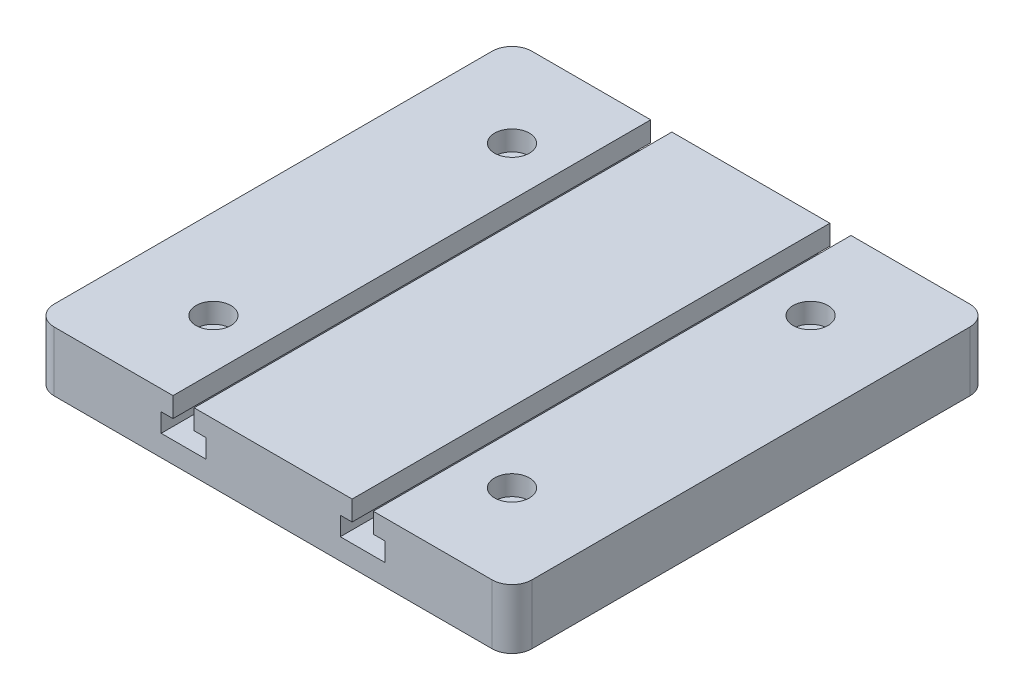
SolidWorks part; units mm, degrees
material "Delrin 2700 NC010, Low Viscosity Acetal Copolymer (SS)"
ref_plane "Front" through (0, 0, 0) normal (0, 0, 1) x (1, 0, 0)
ref_plane "Top" through (0, 0, 0) normal (0, 1, 0) x (1, 0, 0)
ref_plane "Right" through (0, 0, 0) normal (1, 0, 0) x (0, 0, -1)
sketch "Sketch1" plane through (0, 0, 0) normal (0, 1, 0) x (1, 0, 0)
  line L1 (-76.2, 76.2) -> (76.2, 76.2)
  line L2 (-76.2, 76.2) -> (-76.2, -76.2)
  line L3 (-76.2, -76.2) -> (76.2, -76.2)
  line L4 (76.2, 76.2) -> (76.2, -76.2)
  line L5 (-76.2, 76.2) -> (76.2, -76.2) construction
  line L6 (-76.2, -76.2) -> (76.2, 76.2) construction
  point P0 (0, 0)
  dimension "D1" = 152.4
  dimension "D2" = 152.4
extrude "Boss-Extrude1" add sketch "Sketch1" along normal blind 19.05
hole_wizard "CBORE for 1/4 Socket Head Cap Screw1" positions "Sketch2" profile "Sketch3" counterbore size "1/4" standard "ANSI Inch" end condition through all
sketch "Sketch2" plane through (0, 19.05, 0) normal (0, 1, 0) x (1, 0, 0)
  line L1 (-47.625, 47.625) -> (47.625, 47.625) construction
  line L2 (-47.625, 47.625) -> (-47.625, -47.625) construction
  line L3 (-47.625, -47.625) -> (47.625, -47.625) construction
  line L4 (47.625, 47.625) -> (47.625, -47.625) construction
  line L5 (-47.625, 47.625) -> (47.625, -47.625) construction
  line L6 (-47.625, -47.625) -> (47.625, 47.625) construction
  point P0 (-47.625, 47.625)
  point P2 (47.625, 47.625)
  point P4 (47.625, -47.625)
  point P6 (-47.625, -47.625)
  point P108 (0, 0)
  dimension "D1" = 95.25
  dimension "D2" = 95.25
sketch "Sketch3" plane through (-47.625, 19.05, -47.625) normal (1, 0, 0) x (0, 0, 1)
  line L0 (0, 0) -> (0, 19.05)
  line L1 (0, 19.05) -> (3.2639, 19.05)
  line L3 (3.2639, 19.05) -> (3.2639, 6.35)
  line L4 (3.2639, 6.35) -> (5.5562, 6.35)
  line L5 (5.5562, 6.35) -> (5.5562, 0)
  line L7 (5.5562, 0) -> (0, 0)
  line L11 (0, -6.35) -> (0, 107.95) construction
  dimension "Thru Hole Dia." = 6.5278
  dimension "Thru Hole Depth" = 19.05
  dimension "C'Bore Dia." = 11.1125
  dimension "C'Bore Depth" = 6.35
sketch "Sketch4" plane through (0, 0, 76.2) normal (0, 0, 1) x (1, 0, 0)
  line L0 (-31.9484, 19.05) -> (-31.9484, 12.7)
  line L1 (-76.2, 19.05) -> (76.2, 19.05) construction
  line L2 (-31.9484, 12.7) -> (-35.7188, 12.7)
  line L3 (-35.7188, 12.7) -> (-35.7188, 6.7469)
  line L4 (-35.7188, 6.7469) -> (-21.4312, 6.7469)
  line L5 (-21.4312, 6.7469) -> (-21.4312, 12.7)
  line L6 (-21.4312, 12.7) -> (-25.2016, 12.7)
  line L7 (-25.2016, 12.7) -> (-25.2016, 19.05)
  line L8 (0, 0) -> (0, 19.05) construction
  line L9 (-28.575, 6.7469) -> (-28.575, 19.05) construction
  line L10 (28.575, 6.7469) -> (28.575, 19.05) construction
  line L11 (25.2016, 12.7) -> (25.2016, 19.05)
  line L12 (21.4312, 12.7) -> (25.2016, 12.7)
  line L13 (21.4312, 6.7469) -> (21.4312, 12.7)
  line L14 (35.7188, 6.7469) -> (21.4312, 6.7469)
  line L15 (35.7188, 12.7) -> (35.7188, 6.7469)
  line L16 (31.9484, 12.7) -> (35.7188, 12.7)
  line L17 (31.9484, 19.05) -> (31.9484, 12.7)
  line L18 (-31.9484, 19.05) -> (-25.2016, 19.05)
  line L19 (25.2016, 19.05) -> (31.9484, 19.05)
  line L20 (-76.2, 0) -> (76.2, 0) construction
  dimension "D1" = 14.2875
  dimension "D2" = 6.7469
  dimension "D3" = 6.35
  dimension "D4" = 57.15
  dimension "D5" = 5.9531
  dimension "D6" = 6.7469
extrude "T-SLOT CUT WITH MCMASTER 8789A16 BIT" cut sketch "Sketch4" against normal through all
fillet "Fillet1" radius 6.35 4 edges at (-76.2, 9.525, 76.2) (76.2, 9.525, 76.2) (76.2, 9.525, -76.2) (-76.2, 9.525, -76.2)
